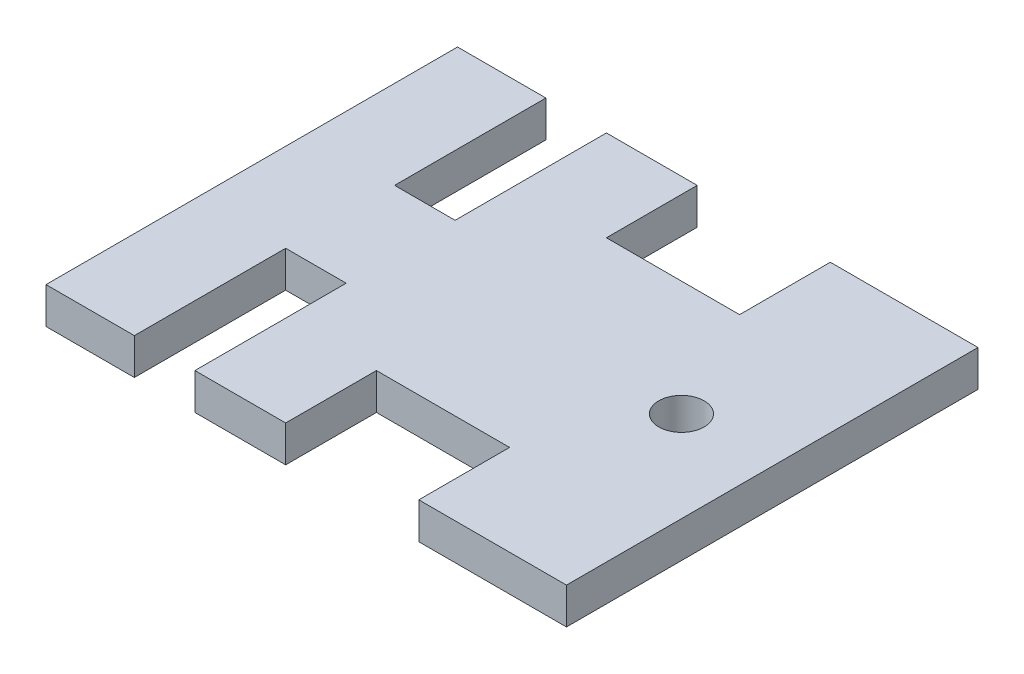
SolidWorks part; units mm, degrees
material "Maple"
ref_plane "Front Plane" through (0, 0, 0) normal (0, 0, 1) x (1, 0, 0)
ref_plane "Top Plane" through (0, 0, 0) normal (0, 1, 0) x (1, 0, 0)
ref_plane "Right Plane" through (0, 0, 0) normal (1, 0, 0) x (0, 0, -1)
sketch "Sketch1" plane through (0, 0, 0) normal (0, 1, 0) x (1, 0, 0)
  line L1 (0, -68) -> (86, -68)
  line L2 (0, -68) -> (0, 0)
  line L3 (0, 0) -> (86, 0)
  line L4 (86, -68) -> (86, 0)
  line L6 (86, -80) -> (86, 12) construction
  dimension "D2" = 68
extrude "Boss-Extrude1" add sketch "Sketch1" along normal blind 6
ref_plane "Plane2" through (0, 0, 34) normal (0, 0, 1) x (1, 0, 0)
ref_plane "Plane1" through (0, 3, 0) normal (0, 1, 0) x (1, 0, 0)
sketch "Sketch2" plane through (0, 6, 0) normal (0, 1, 0) x (1, 0, 0)
  line L0 (50.6, 19.4) -> (50.6, -68) construction
  line L1 (19.6, 63.4) -> (19.6, -68) construction
  line L3 (0, -68) -> (86, -68) construction
  line L5 (54.6, 19.4) -> (46.6, 19.4) construction
  line L6 (24.6, -68) -> (14.6, -68)
  line L7 (24.6, -68) -> (24.6, -43)
  line L8 (24.6, -43) -> (14.6, -43)
  line L9 (14.6, -68) -> (14.6, -43)
  line L10 (61.6, -68) -> (39.6, -68)
  line L11 (61.6, -68) -> (61.6, -53)
  line L12 (61.6, -53) -> (39.6, -53)
  line L13 (39.6, -68) -> (39.6, -53)
  line L14 (23.6, 63.4) -> (15.6, 63.4) construction
  dimension "D1" = 10
  dimension "D2" = 25
  dimension "D3" = 22
  dimension "D4" = 15
extrude "Cut-Extrude1" cut sketch "Sketch2" against normal through all
mirror "Mirror1" about plane through (0, 0, 34) normal (0, 0, 1) of "Cut-Extrude1"
hole_wizard "Ø7.5 (7.5) Diameter Hole1" positions "Sketch4" profile "Sketch3" hole size "Ø7.5" standard "ANSI Metric" end condition through all
sketch "Sketch4" plane through (0, 0, 0) normal (0, -1, 0) x (-1, 0, 0)
  circle A0 centre (-71, -34) radius 4 construction
  point P0 (-71, -34)
sketch "Sketch3" plane through (71, 0, 34) normal (1, 0, 0) x (0, 0, -1)
  line L0 (0, 0) -> (0, 6)
  line L1 (0, 6) -> (3.75, 6)
  line L2 (3.75, 6) -> (3.75, 0)
  line L5 (3.75, 0) -> (0, 0)
  line L11 (0, -6.35) -> (0, 107.95) construction
  dimension "Thru Hole Dia." = 7.5
  dimension "Thru Hole Depth" = 6
